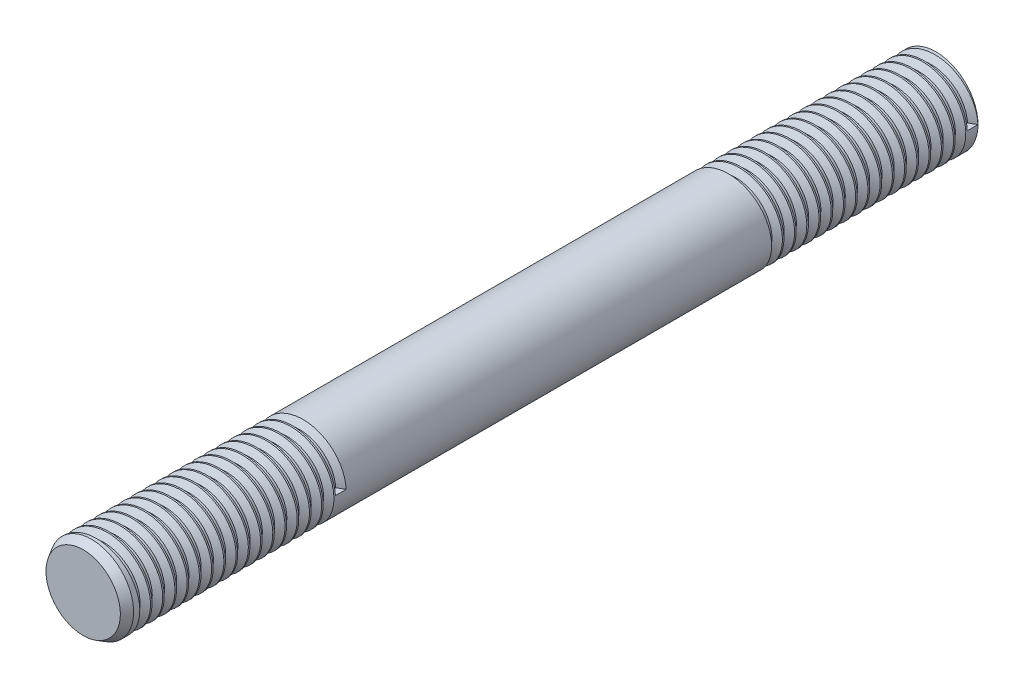
SolidWorks part; units mm, degrees
material "A-1"
ref_plane "Front Plane" through (0, 0, 0) normal (0, 0, 1) x (1, 0, 0)
ref_plane "Top Plane" through (0, 0, 0) normal (0, 1, 0) x (1, 0, 0)
ref_plane "Right Plane" through (0, 0, 0) normal (1, 0, 0) x (0, 0, -1)
sketch "Sketch1" plane through (0, 0, 0) normal (0, 0, 1) x (1, 0, 0)
  circle A0 centre (0, 0) radius 7.9375
  dimension "D1" = 15.875
extrude "Boss-Extrude1" add sketch "Sketch1" along normal mid plane 161.925 contours A0
ref_plane "Plane1" through (0, 0, 79.375) normal (0, 0, 1) x (1, 0, 0)
chamfer "Chamfer1" distance 1.5875 angle 30 2 edges at (7.9375, 0, -80.9625) (7.9375, 0, 80.9625) first distance on face at (7.9375, 0, -80.9625) first distance on face at (7.9375, 0, 80.9625)
thread "Thread1" pitch 2.3091 method cut profile "Thread Profile1" start angle 0, offset 0, length 38.1, pitch 2.3091, diameter 15.875
ref_plane "Plane2" through (-7.9375, 0, 79.375) normal (0, -1, 0) x (-1, 0, 0)
sketch "Thread Profile1" plane through (-7.9375, 0, 79.375) normal (0, -1, 0) x (-1, 0, 0)
  line L0 (0, 0) -> (0, 2.3091) construction
  line L11 (0, 0) -> (0, 2.0205)
  line L12 (0, 2.0205) -> (-1.2498, 1.2989)
  line L13 (-1.2498, 1.2989) -> (-1.2498, 0.7216)
  line L15 (-1.2498, 0.7216) -> (0, 0)
  line L17 (-1.2498, 1.0102) -> (0, 1.0102) construction
  point P2 (0, 0)
  dimension "Pitch" = 2.3091
  dimension "Profile_Angle" = 60
  dimension "Profile_Land" = 0.5773
  dimension "Profile_Height" = 1.2498
ref_plane "Plane3" through (0, 0, -79.375) normal (0, 0, 1) x (1, 0, 0)
thread "Thread2" pitch 2.3091 method cut profile "Thread Profile2" start angle 0, offset 0, length 38.1, pitch 2.3091, diameter 15.875
ref_plane "Plane4" through (7.9375, 0, -80.046) normal (0, -1, 0) x (1, 0, 0)
sketch "Thread Profile2" plane through (7.9375, 0, -80.046) normal (0, -1, 0) x (1, 0, 0)
  line L0 (0, 0) -> (0, 2.3091) construction
  line L11 (0, 0) -> (0, 2.0205)
  line L12 (0, 2.0205) -> (-1.2498, 1.2989)
  line L13 (-1.2498, 1.2989) -> (-1.2498, 0.7216)
  line L15 (-1.2498, 0.7216) -> (0, 0)
  line L17 (-1.2498, 1.0102) -> (0, 1.0102) construction
  point P2 (0, 0)
  dimension "Pitch" = 2.3091
  dimension "Profile_Angle" = 60
  dimension "Profile_Land" = 0.5773
  dimension "Profile_Height" = 1.2498
